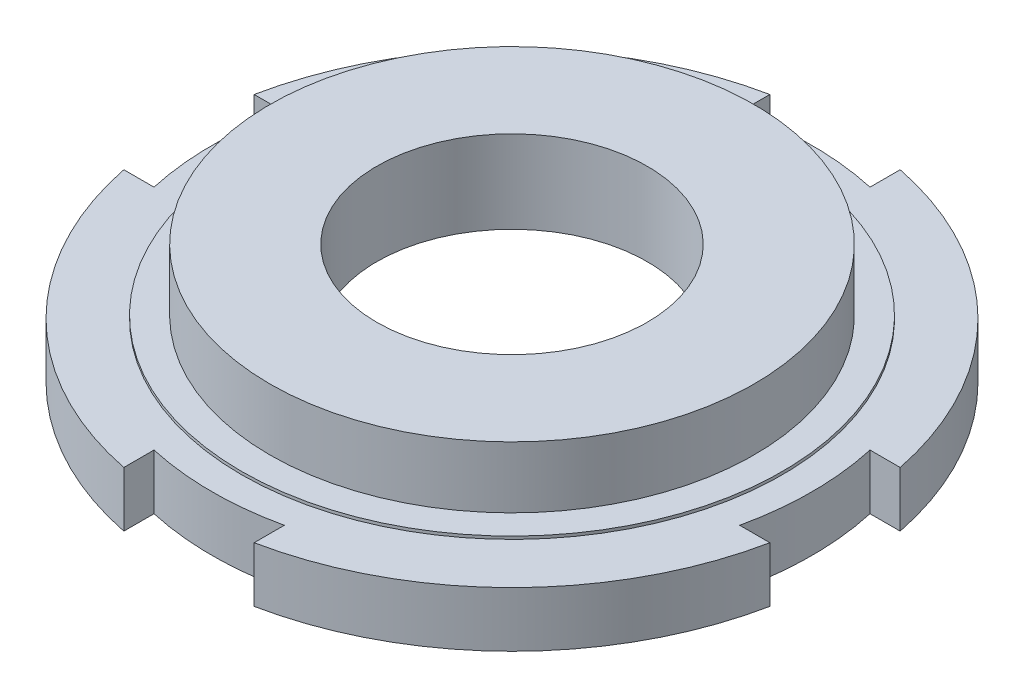
SolidWorks part; units mm, degrees
ref_plane "Front Plane" through (0, 0, 0) normal (0, 0, 1) x (1, 0, 0)
ref_plane "Top Plane" through (0, 0, 0) normal (0, 1, 0) x (1, 0, 0)
ref_plane "Right Plane" through (0, 0, 0) normal (1, 0, 0) x (0, 0, -1)
sketch "Sketch1" plane through (0, 0, 0) normal (0, 1, 0) x (1, 0, 0)
  line L0 (30.2481, 6.731) -> (33.3638, 6.731)
  line L1 (30.2481, -6.731) -> (33.3638, -6.731)
  line L2 (-55, 0) -> (55, 0) construction
  line L3 (6.731, -30.2481) -> (6.731, -33.3638)
  line L4 (-6.731, -30.2481) -> (-6.731, -33.3638)
  line L5 (-30.2481, -6.731) -> (-33.3638, -6.731)
  line L6 (-30.2481, 6.731) -> (-33.3638, 6.731)
  line L7 (-6.731, 30.2481) -> (-6.731, 33.3638)
  line L8 (6.731, 30.2481) -> (6.731, 33.3638)
  arc A1 (-33.3638, -6.731) -> (-6.731, -33.3638) centre (0, 0) ccw
  circle A2 centre (0, 0) radius 13.97
  arc A3 (-30.2481, 6.731) -> (-30.2481, -6.731) centre (0, 0) ccw
  arc A4 (6.731, 30.2481) -> (-6.731, 30.2481) centre (0, 0) ccw
  arc A5 (30.2481, -6.731) -> (30.2481, 6.731) centre (0, 0) ccw
  arc A6 (-6.731, -30.2481) -> (6.731, -30.2481) centre (0, 0) ccw
  arc A7 (6.731, -33.3638) -> (33.3638, -6.731) centre (0, 0) ccw
  arc A8 (33.3638, 6.731) -> (6.731, 33.3638) centre (0, 0) ccw
  arc A9 (-6.731, 33.3638) -> (-33.3638, 6.731) centre (0, 0) ccw
  point P26 (0, 0)
  dimension "D1" = 68.072
  dimension "D2" = 61.976
  dimension "D6" = 27.94
  dimension "D3" = 13.462
  dimension "D4" = 6.731
  dimension "D5" = 4
ref_axis "Axis1" through (41.3265, 0, 0) along (-1, 0, 0)
ref_plane "Plane2" through (0, 0, 0) normal (0, -0.9903, 0.1392) x (-1, 0, 0)
ref_plane "Plane3" through (0, 6.2882, -0.8837) normal (0, -0.9903, 0.1392) x (-1, 0, 0)
extrude "Boss-Extrude2" add sketch "Sketch1" along normal blind 6
sketch "Sketch2" plane through (0, 0, 0) normal (0, -1, 0) x (1, 0, 0)
  line L3 (13.4704, -13.4704) -> (-11.5106, -38.4514)
  line L4 (-16.7285, -36.4851) -> (0.7202, -19.0364)
  line L5 (6.7925, 0) -> (-6.7925, 0) construction
  arc A3 (0.7202, -19.0364) -> (13.4704, -13.4704) centre (0, 0) cw
  arc A4 (-11.5106, -38.4514) -> (-16.7285, -36.4851) centre (0, 0) cw
  point P4 (0.9799, -25.9609)
  dimension "D1" = 19.05
  dimension "D2" = 5.08
  dimension "D3" = 45
extrude "Cut-Extrude1" cut sketch "Sketch2" against normal blind 3.81
sketch "Sketch3" plane through (0, 0, 0) normal (0, -1, 0) x (1, 0, 0)
  circle A0 centre (0, 0) radius 27.94
  dimension "D1" = 55.88
extrude "Cut-Extrude2" cut sketch "Sketch3" against normal blind 0.3
sketch "Sketch5" plane through (0, 6, 0) normal (0, 1, 0) x (1, 0, 0)
  circle A0 centre (0, 0) radius 25.0063
  circle A1 centre (0, 0) radius 13.97 construction
  circle A2 centre (0, 0) radius 13.97
  dimension "D1" = 50.0126
extrude "Boss-Extrude3" add sketch "Sketch5" along normal blind 6.35
sketch "Sketch6" plane through (0, 6, 0) normal (0, 1, 0) x (1, 0, 0)
  circle A0 centre (0, 0) radius 27.94
  circle A3 centre (0, 0) radius 50.8
  dimension "D1" = 55.88
  dimension "D2" = 101.6
extrude "Cut-Extrude3" cut sketch "Sketch6" against normal blind 0.3
